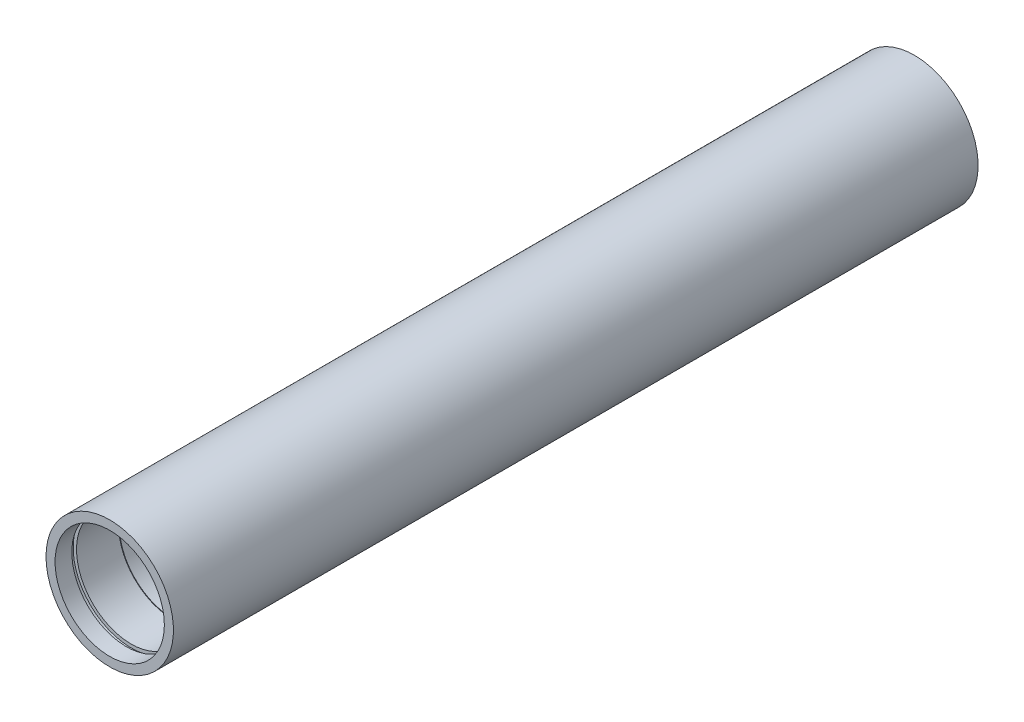
SolidWorks part; units mm, degrees
ref_plane "Front Plane" through (0, 0, 0) normal (1, 0, 0) x (0, 1, 0)
ref_plane "Top Plane" through (0, 0, 0) normal (0, 0, 1) x (0, 1, 0)
ref_plane "Right Plane" through (0, 0, 0) normal (0, 1, 0) x (-1, 0, 0)
sketch "Sketch2" plane through (0, 0, 0) normal (0, 0, 1) x (0, 1, 0)
  line L0 (0, 0) -> (24.13, 0) construction
  circle A0 centre (0, 0) radius 24.13
  circle A1 centre (0, 0) radius 20.447
  dimension "D1" = 40.894
  dimension "D2" = 48.26
extrude "base" add sketch "Sketch2" along normal blind 304.8
sketch "Sketch3" plane through (0, 0, 0) normal (0, 0, -1) x (1, 0, 0)
  circle A0 centre (0, 0) radius 21.9075
  circle A1 centre (0, 0) radius 20.447
  circle A2 centre (0, 0) radius 20.447 construction
  dimension "D1" = 43.815
extrude "bulkhead_snap_ring_groove" cut sketch "Sketch3" against normal blind 1.7272 from offset 6.35 offset against normal yes
sketch "Sketch4" plane through (0, 0, 0) normal (0, 0, -1) x (1, 0, 0)
  circle A0 centre (0, 0) radius 20.701
  dimension "D1" = 41.402
extrude "bulkhead_seating_bore" cut sketch "Sketch4" against normal offset from surface (17.7292 mm away) 9.652 from offset 0 up to face at (-20.447, 0, 8.0772)
sketch "Sketch6" plane through (0, 0, 304.8) normal (0, 0, 1) x (1, 0, 0)
  circle A0 centre (0, 0) radius 21.971
  dimension "D1" = 43.942
extrude "nozzle_snap_ring_groove" cut sketch "Sketch6" against normal blind 1.778 from offset 6.35 offset against normal yes
sketch "Sketch5" plane through (0, 0, 304.8) normal (0, 0, 1) x (1, 0, 0)
  circle A0 centre (0, 0) radius 20.701
  dimension "D1" = 41.402
extrude "nozzle_seating_bore" cut sketch "Sketch5" against normal offset from surface (24.0665 mm away) 15.9385 up to face at (20.447, 0, 296.672)
equation "\"snapring\"=1.725"
equation "\"snapringdepth\"=0.068"
equation "\"snapringoffset\"=0.25"
